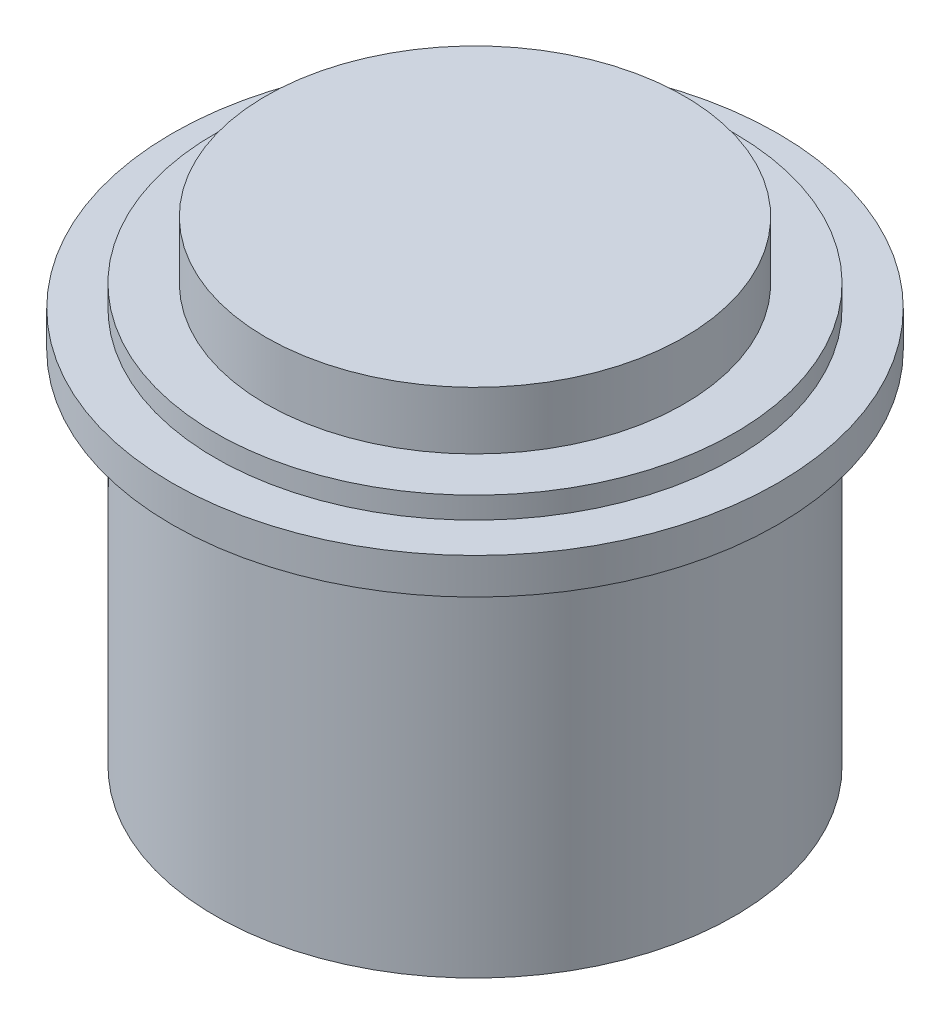
SolidWorks part; units mm, degrees
ref_plane "前视基准面" through (0, 0, 0) normal (0, 0, 1) x (1, 0, 0)
ref_plane "上视基准面" through (0, 0, 0) normal (0, 1, 0) x (1, 0, 0)
ref_plane "右视基准面" through (0, 0, 0) normal (1, 0, 0) x (0, 0, -1)
sketch "草图2" plane through (0, 0, 0) normal (0, 1, 0) x (1, 0, 0)
  circle A0 centre (-35.4839, -6.1271) radius 29
  circle A1 centre (-35.4839, -6.1271) radius 36
  circle A2 centre (-35.4839, -6.1271) radius 42
  dimension "D1" = 7
  dimension "72" = 72
  dimension "D2" = 6
extrude "凸台-拉伸1" add sketch "草图2" along normal blind 66 contours A0 region at (-35.4839, 0, 6.1271)
extrude "凸台-拉伸2" add sketch "草图2<3>" along normal blind 58 contours A1
sketch "草图2<3>" plane through (0, 0, 0) normal (0, 1, 0) x (1, 0, 0) same geometry as "草图2"
extrude "凸台-拉伸3" add sketch "草图2<4>" along normal blind 5 from offset 50 contours A2 A1 region at (-76.296, 0, 6.1271)
sketch "草图2<4>" plane through (0, 0, 0) normal (0, 1, 0) x (1, 0, 0) same geometry as "草图2"
